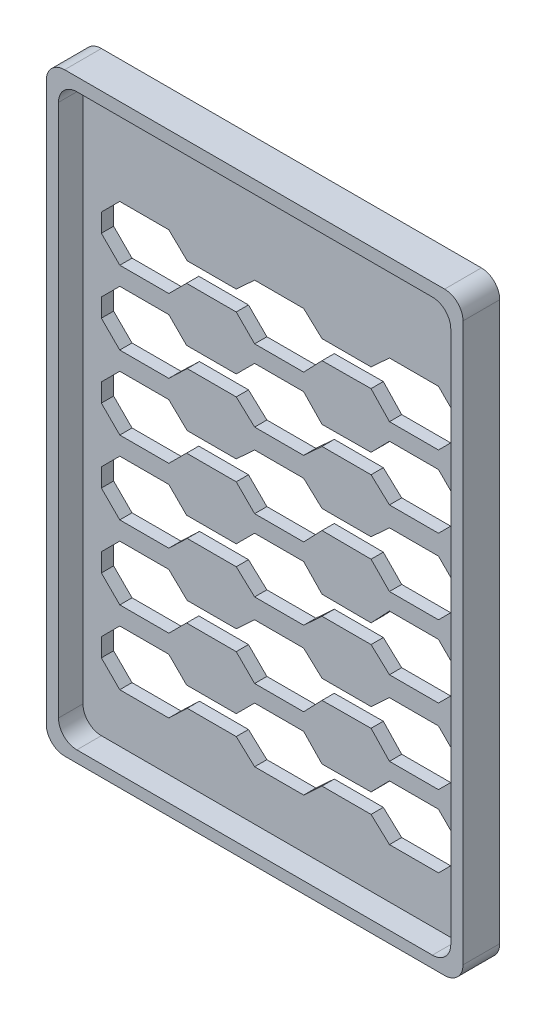
SolidWorks part; units mm, degrees
ref_plane "Front Plane" through (0, 0, 0) normal (1, 0, 0) x (0, 1, 0)
ref_plane "Top Plane" through (0, 0, 0) normal (0, 0, 1) x (0, 1, 0)
ref_plane "Right Plane" through (0, 0, 0) normal (0, 1, 0) x (-1, 0, 0)
sketch "Sketch1" plane through (0, 0, 0) normal (0, 0, 1) x (0, 1, 0)
  line L0 (-57.553, 0) -> (64.8653, 0) construction
  line L6 (46.3828, -29.0087) -> (46.3828, 29.0087)
  line L20 (-46.6172, -29.0087) -> (-46.6172, 29.0087)
  line L21 (46.5, -32) -> (-46.5, 32) construction
  line L38 (46.5, 32) -> (-46.5, -32) construction
  line L39 (45.5, -34) -> (-45.5, -34)
  line L48 (48.5, -31) -> (48.5, 31)
  line L49 (45.5, 34) -> (-45.5, 34)
  line L50 (-48.5, -31) -> (-48.5, 31)
  line L51 (48.5, -34) -> (-48.5, 34) construction
  line L52 (48.5, 34) -> (-48.5, -34) construction
  line L53 (27.2656, -29) -> (24.2656, -29)
  line L54 (43.3828, 32.0087) -> (-43.6172, 32.0087)
  line L55 (43.3828, -32.0087) -> (-43.6172, -32.0087)
  line L56 (-38.6172, 26.0087) -> (-38.6172, 18.0087)
  line L57 (-38.6172, 18.0087) -> (-35.7344, 15)
  line L59 (-32.5, 15.1085) -> (-29.6085, 18)
  line L60 (-29.6085, 18) -> (-29.6085, 26)
  line L61 (-29.6085, 26) -> (-32.6172, 29.0087)
  line L62 (-32.6172, 29.0087) -> (-35.6172, 29.0087)
  line L63 (-35.6172, 29.0087) -> (-38.6172, 26.0087)
  line L64 (-35.7344, 15) -> (-35.7344, 7)
  line L65 (-32.5, 15.1085) -> (-32.5, 7)
  line L66 (-38.5, 4) -> (-38.5, -4)
  line L67 (-38.5, -4) -> (-35.7344, -7)
  line L68 (30.2656, -26) -> (27.2656, -29)
  line L69 (-32.6172, -7) -> (-29.5, -4)
  line L70 (-29.5, -4) -> (-29.5, 4)
  line L71 (-29.5, 4) -> (-32.5, 7)
  line L72 (24.2656, -29) -> (21.2656, -26)
  line L73 (-35.7344, 7) -> (-38.5, 4)
  line L74 (-35.7344, -7) -> (-35.7344, -15)
  line L75 (-32.6172, -7) -> (-32.564, -14.9998)
  line L76 (-38.5, -18) -> (-38.5, -26)
  line L77 (-38.5, -26) -> (-35.5, -29)
  line L78 (-35.5, -29) -> (-32.5, -29)
  line L79 (-32.5, -29) -> (-29.5, -26)
  line L80 (-29.5, -26) -> (-29.5, -18)
  line L81 (-29.5, -18) -> (-32.564, -14.9998)
  line L83 (-35.7344, -15) -> (-38.5, -18)
  line L84 (-28.1172, 52.6189) -> (-28.1172, -50.5455) construction
  line L85 (-20.7344, -29) -> (-23.7344, -29)
  line L86 (-23.7344, -29) -> (-26.7344, -26)
  line L87 (-17.7344, -26) -> (-20.7344, -29)
  line L88 (-17.7344, -18) -> (-17.7344, -26)
  line L89 (-26.7344, -26) -> (-26.7344, -18)
  line L90 (-26.7344, -18) -> (-23.5641, -14.9989)
  line L91 (-20.5, -15) -> (-17.7344, -18)
  line L92 (12.5, -29) -> (15.5, -29)
  line L93 (-20.5, -7) -> (-20.5, -15)
  line L94 (-23.6172, -7) -> (-23.5641, -14.9989)
  line L95 (-23.6172, -7) -> (-26.7344, -4)
  line L96 (9.5, -26) -> (12.5, -29)
  line L97 (-17.7344, -4) -> (-20.5, -7)
  line L98 (-20.5, 7) -> (-17.7344, 4)
  line L99 (-17.7344, 4) -> (-17.7344, -4)
  line L100 (-26.7344, -4) -> (-26.7344, 4)
  line L101 (-26.7344, 4) -> (-23.7344, 7)
  line L102 (15.5, -29) -> (18.5, -26)
  line L103 (-20.5, 15) -> (-20.5, 7)
  line L104 (-23.7344, 15.1085) -> (-23.7344, 7)
  line L105 (27.5, -15) -> (30.2656, -18)
  line L106 (-23.7344, 15.1085) -> (-26.6259, 18)
  line L107 (-17.6172, 18.0087) -> (-20.5, 15)
  line L108 (-17.6172, 26.0087) -> (-17.6172, 18.0087)
  line L109 (-26.6259, 18) -> (-26.6259, 26)
  line L110 (-26.6259, 26) -> (-23.6172, 29.0087)
  line L111 (-20.6172, 29.0087) -> (-17.6172, 26.0087)
  line L112 (-23.6172, 29.0087) -> (-20.6172, 29.0087)
  line L113 (-16.1172, 52.6189) -> (-16.1172, -50.5455) construction
  line L114 (30.2656, -18) -> (30.2656, -26)
  line L115 (7.8828, 52.6189) -> (7.8828, -50.5455) construction
  line L116 (19.8828, 52.6189) -> (19.8828, -50.5455) construction
  line L117 (-8.6172, -7) -> (-8.6703, -14.9989)
  line L118 (-11.7344, -7) -> (-11.7344, -15)
  line L119 (-11.7344, -15) -> (-14.5, -18)
  line L120 (-5.5, -18) -> (-8.6703, -14.9989)
  line L121 (-5.5, -26) -> (-5.5, -18)
  line L122 (-14.5, -18) -> (-14.5, -26)
  line L123 (-14.5, -26) -> (-11.5, -29)
  line L124 (-8.5, -29) -> (-5.5, -26)
  line L125 (-11.5, -29) -> (-8.5, -29)
  line L126 (-14.5, -4) -> (-11.7344, -7)
  line L127 (-8.6172, -7) -> (-5.5, -4)
  line L128 (-5.5, -4) -> (-5.5, 4)
  line L129 (-14.5, 4) -> (-14.5, -4)
  line L130 (-5.5, 4) -> (-8.5, 7)
  line L131 (-11.7344, 7) -> (-14.5, 4)
  line L132 (-8.5, 15.1085) -> (-8.5, 7)
  line L133 (-11.7344, 15) -> (-11.7344, 7)
  line L134 (-8.5, 15.1085) -> (-5.6085, 18)
  line L135 (-14.6172, 18.0087) -> (-11.7344, 15)
  line L136 (-14.6172, 26.0087) -> (-14.6172, 18.0087)
  line L137 (-5.6085, 18) -> (-5.6085, 26)
  line L138 (-5.6085, 26) -> (-8.6172, 29.0087)
  line L139 (-8.6172, 29.0087) -> (-11.6172, 29.0087)
  line L140 (-11.6172, 29.0087) -> (-14.6172, 26.0087)
  line L141 (0.2656, -29) -> (-2.7344, -26)
  line L142 (3.2656, -29) -> (0.2656, -29)
  line L143 (6.2656, -26) -> (3.2656, -29)
  line L144 (6.2656, -18) -> (6.2656, -26)
  line L145 (-2.7344, -26) -> (-2.7344, -18)
  line L146 (-2.7344, -18) -> (0.3296, -14.9998)
  line L147 (3.5, -15) -> (6.2656, -18)
  line L148 (3.5, -7) -> (3.5, -15)
  line L149 (0.3828, -7) -> (0.3296, -14.9998)
  line L150 (0.3828, -7) -> (-2.7344, -4)
  line L151 (6.2656, -4) -> (3.5, -7)
  line L152 (6.2656, 4) -> (6.2656, -4)
  line L153 (-2.7344, -4) -> (-2.7344, 4)
  line L154 (3.5, 7) -> (6.2656, 4)
  line L155 (-2.7344, 4) -> (0.2656, 7)
  line L156 (3.5, 15) -> (3.5, 7)
  line L157 (0.2656, 15.1085) -> (0.2656, 7)
  line L158 (0.2656, 15.1085) -> (-2.6259, 18)
  line L159 (6.3828, 18.0087) -> (3.5, 15)
  line L160 (6.3828, 26.0087) -> (6.3828, 18.0087)
  line L161 (-2.6259, 18) -> (-2.6259, 26)
  line L162 (-2.6259, 26) -> (0.3828, 29.0087)
  line L163 (3.3828, 29.0087) -> (6.3828, 26.0087)
  line L164 (0.3828, 29.0087) -> (3.3828, 29.0087)
  line L165 (21.2656, -26) -> (21.2656, -18)
  line L166 (21.2656, -18) -> (24.4359, -14.9989)
  line L167 (18.5, -18) -> (15.436, -14.9998)
  line L168 (18.5, -26) -> (18.5, -18)
  line L169 (9.5, -18) -> (9.5, -26)
  line L170 (12.2656, -15) -> (9.5, -18)
  line L171 (12.2656, -7) -> (12.2656, -15)
  line L172 (15.3828, -7) -> (15.436, -14.9998)
  line L173 (24.3828, -7) -> (24.4359, -14.9989)
  line L174 (27.5, -7) -> (27.5, -15)
  line L175 (30.2656, -4) -> (27.5, -7)
  line L176 (24.3828, -7) -> (21.2656, -4)
  line L177 (15.3828, -7) -> (18.5, -4)
  line L178 (9.5, -4) -> (12.2656, -7)
  line L179 (9.5, 4) -> (9.5, -4)
  line L180 (12.2656, 7) -> (9.5, 4)
  line L181 (18.5, 4) -> (15.5, 7)
  line L182 (18.5, -4) -> (18.5, 4)
  line L183 (21.2656, -4) -> (21.2656, 4)
  line L184 (30.2656, 4) -> (30.2656, -4)
  line L185 (27.5, 7) -> (30.2656, 4)
  line L186 (21.2656, 4) -> (24.2656, 7)
  line L187 (27.5, 15) -> (27.5, 7)
  line L188 (24.2656, 15.1085) -> (24.2656, 7)
  line L189 (12.2656, 15) -> (12.2656, 7)
  line L190 (15.5, 15.1085) -> (15.5, 7)
  line L191 (12.3828, 29.0087) -> (9.3828, 26.0087)
  line L192 (9.3828, 26.0087) -> (9.3828, 18.0087)
  line L193 (9.3828, 18.0087) -> (12.2656, 15)
  line L194 (15.5, 15.1085) -> (18.3915, 18)
  line L195 (18.3915, 18) -> (18.3915, 26)
  line L196 (18.3915, 26) -> (15.3828, 29.0087)
  line L197 (15.3828, 29.0087) -> (12.3828, 29.0087)
  line L198 (30.3828, 18.0087) -> (27.5, 15)
  line L199 (24.2656, 15.1085) -> (21.3741, 18)
  line L200 (30.3828, 26.0087) -> (30.3828, 18.0087)
  line L201 (21.3741, 18) -> (21.3741, 26)
  line L202 (21.3741, 26) -> (24.3828, 29.0087)
  line L203 (27.3828, 29.0087) -> (30.3828, 26.0087)
  line L204 (24.3828, 29.0087) -> (27.3828, 29.0087)
  line L205 (-28.6085, 26) -> (-27.6085, 26)
  arc A0 (-43.6172, 32.0087) -> (-46.6172, 29.0087) centre (-43.6172, 29.0087) ccw
  arc A2 (-45.5, 34) -> (-48.5, 31) centre (-45.5, 31) ccw
  arc A3 (43.3828, 32.0087) -> (46.3828, 29.0087) centre (43.3828, 29.0087) cw
  arc A6 (45.5, 34) -> (48.5, 31) centre (45.5, 31) cw
  arc A7 (45.5, -34) -> (48.5, -31) centre (45.5, -31) ccw
  arc A8 (43.3828, -32.0087) -> (46.3828, -29.0087) centre (43.3828, -29.0087) ccw
  arc A9 (-43.6172, -32.0087) -> (-46.6172, -29.0087) centre (-43.6172, -29.0087) cw
  arc A10 (-45.5, -34) -> (-48.5, -31) centre (-45.5, -31) cw
  point P0 (0, 0)
  point P6 (0, 0)
  point P69 (-37.1172, 27.5087)
  dimension "D7" = 8
  dimension "D5" = 3
  dimension "D6" = 3
  dimension "D1" = 64
  dimension "D2" = 93
  dimension "D3" = 68
  dimension "D4" = 97
  dimension "D8" = 3
  dimension "D9" = 30.5
  dimension "D10" = 3
  dimension "D11" = 135
  dimension "D12" = 135
  dimension "D13" = 1
  dimension "D14" = 1
  dimension "D16" = 8
  dimension "D17" = 3
  dimension "D18" = 54.5
  dimension "D19" = 66.5
  dimension "D23" = 3
  dimension "D24" = 8
  dimension "D30" = 8
  dimension "D32" = 8
  dimension "D33" = 8
  dimension "D34" = 8
  dimension "D35" = 8
  dimension "D37" = 3
  dimension "D40" = 135
  dimension "D41" = 135
  dimension "D42" = 18.5
extrude "Boss-Extrude1" add sketch "Sketch1" along normal blind 6 contours A10 L39 A7 L48 A6 L49 A2 L50 L55 A9 L20 A0 L54 A3 L6 A8 region at (32.8154, 0, 0)
extrude "Boss-Extrude2" add sketch "Sketch1<3>" along normal blind 2 contours A9 L55 A8 L6 A3 L54 A0 L20 L197 L196 L195 L194 L190 L181 L182 L177 L172 L167 L168 L102 L92 L96 L169 L170 L171 L178 L179 L180 L189 L193 L192 L191 L140 L139 L138 L137 L134 L132 L130 L128 L127 L117 L120 L121 L124 L125 region at (30.3317, 44.7058, 0)
sketch "Sketch1<3>" plane through (0, 0, 0) normal (0, 0, 1) x (0, 1, 0) same geometry as "Sketch1"
